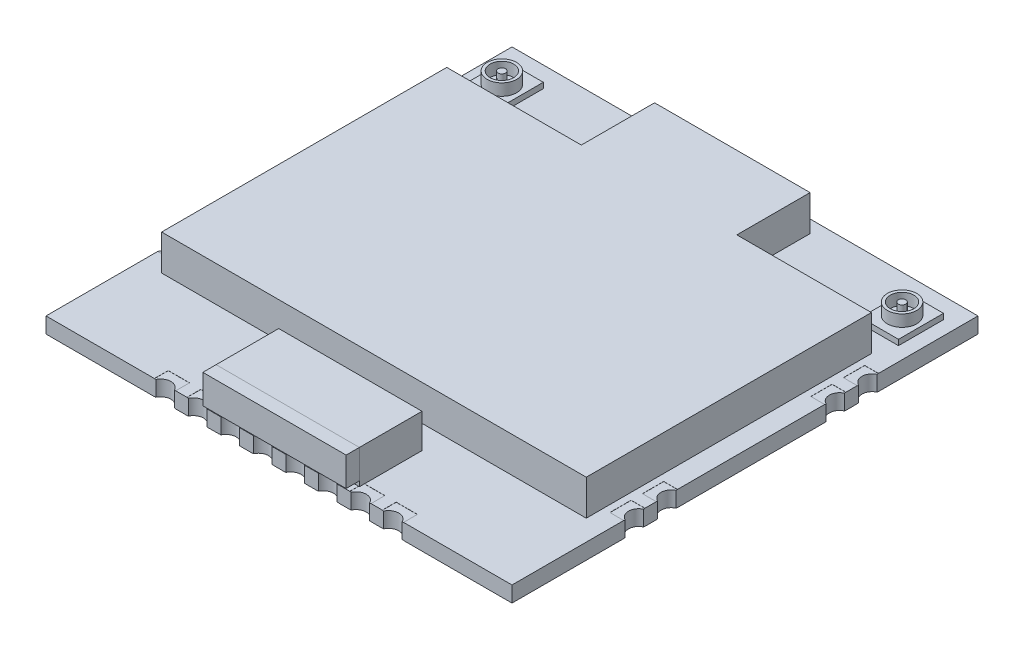
SolidWorks part; units mm, degrees
ref_plane "Front Plane" through (0, 0, 0) normal (0, 0, 1) x (1, 0, 0)
ref_plane "Top Plane" through (0, 0, 0) normal (0, 1, 0) x (1, 0, 0)
ref_plane "Right Plane" through (0, 0, 0) normal (1, 0, 0) x (0, 0, -1)
sketch "Sketch1" plane through (0, 0, 0) normal (0, 1, 0) x (1, 0, 0)
  line L0 (-0.039, 840.9703) -> (812.761, 840.9703) construction
  line L1 (-28.3029, -414.02) -> (-28.3029, -406.4) construction
  line L2 (406.4, 406.4) -> (44.4319, 406.4)
  line L3 (406.4, 406.4) -> (406.4, 230.4034)
  line L4 (406.4, -406.4) -> (214.884, -406.4)
  line L5 (-406.4, 406.4) -> (-406.4, 230.4034)
  line L6 (406.4, 406.4) -> (-406.4, -406.4) construction
  line L7 (406.4, -406.4) -> (-406.4, 406.4) construction
  line L8 (-414.02, -193.04) -> (-406.4, -193.04) construction
  line L9 (-85.1202, -414.02) -> (-85.1202, -406.4) construction
  line L10 (-141.9376, -414.02) -> (-141.9376, -406.4) construction
  line L11 (-198.755, -414.02) -> (-198.755, -406.4) construction
  line L12 (0, 0) -> (0, 406.4) construction
  line L13 (198.755, -414.02) -> (198.755, -406.4) construction
  line L14 (141.9376, -414.02) -> (141.9376, -406.4) construction
  line L15 (85.1202, -414.02) -> (85.1202, -406.4) construction
  line L16 (28.3029, -414.02) -> (28.3029, -406.4) construction
  line L17 (-28.3029, -406.4) -> (-44.4319, -406.4) construction
  line L18 (-44.4319, -406.4) -> (-68.9912, -406.4)
  line L19 (-12.1739, -406.4) -> (-28.3029, -406.4) construction
  line L20 (-68.9912, -406.4) -> (-85.1202, -406.4) construction
  line L21 (-101.2492, -406.4) -> (-125.8086, -406.4)
  line L22 (-85.1202, -406.4) -> (-101.2492, -406.4) construction
  line L23 (-125.8086, -406.4) -> (-141.9376, -406.4) construction
  line L24 (-158.0666, -406.4) -> (-182.626, -406.4)
  line L25 (-141.9376, -406.4) -> (-158.0666, -406.4) construction
  line L26 (-182.626, -406.4) -> (-198.755, -406.4) construction
  line L27 (-214.884, -406.4) -> (-406.4, -406.4)
  line L28 (-198.755, -406.4) -> (-214.884, -406.4) construction
  line L29 (44.4319, -406.4) -> (28.3029, -406.4) construction
  line L30 (12.1739, -406.4) -> (-12.1739, -406.4)
  line L31 (28.3029, -406.4) -> (12.1739, -406.4) construction
  line L32 (101.2492, -406.4) -> (85.1202, -406.4) construction
  line L33 (68.9912, -406.4) -> (44.4319, -406.4)
  line L34 (85.1202, -406.4) -> (68.9912, -406.4) construction
  line L35 (158.0666, -406.4) -> (141.9376, -406.4) construction
  line L36 (125.8086, -406.4) -> (101.2492, -406.4)
  line L37 (141.9376, -406.4) -> (125.8086, -406.4) construction
  line L38 (214.884, -406.4) -> (198.755, -406.4) construction
  line L39 (182.626, -406.4) -> (158.0666, -406.4)
  line L40 (198.755, -406.4) -> (182.626, -406.4) construction
  line L41 (-414.02, -136.2456) -> (-406.4, -136.2456) construction
  line L42 (-414.02, 157.48) -> (-406.4, 157.48) construction
  line L43 (-414.02, 214.2744) -> (-406.4, 214.2744) construction
  line L45 (414.02, 214.2744) -> (406.4, 214.2744) construction
  line L46 (414.02, 157.48) -> (406.4, 157.48) construction
  line L47 (414.02, -136.2456) -> (406.4, -136.2456) construction
  line L48 (414.02, -193.04) -> (406.4, -193.04) construction
  line L49 (-406.4, -193.04) -> (-406.4, -209.169) construction
  line L50 (-406.4, -209.169) -> (-406.4, -406.4)
  line L51 (-406.4, -176.911) -> (-406.4, -193.04) construction
  line L52 (-406.4, -136.2456) -> (-406.4, -152.3746) construction
  line L53 (-406.4, -152.3746) -> (-406.4, -176.911)
  line L54 (-406.4, -120.1166) -> (-406.4, -136.2456) construction
  line L55 (-406.4, 157.48) -> (-406.4, 141.351) construction
  line L56 (-406.4, 141.351) -> (-406.4, -120.1166)
  line L57 (-406.4, 173.609) -> (-406.4, 157.48) construction
  line L58 (-406.4, 214.2744) -> (-406.4, 198.1454) construction
  line L59 (-406.4, 198.1454) -> (-406.4, 173.609)
  line L60 (-406.4, 230.4034) -> (-406.4, 214.2744) construction
  line L61 (406.4, -176.911) -> (406.4, -193.04) construction
  line L62 (406.4, -209.169) -> (406.4, -406.4)
  line L63 (406.4, -193.04) -> (406.4, -209.169) construction
  line L64 (406.4, -120.1166) -> (406.4, -136.2456) construction
  line L65 (406.4, -152.3746) -> (406.4, -176.911)
  line L66 (406.4, -136.2456) -> (406.4, -152.3746) construction
  line L67 (406.4, 173.609) -> (406.4, 157.48) construction
  line L68 (406.4, 141.351) -> (406.4, -120.1166)
  line L69 (406.4, 157.48) -> (406.4, 141.351) construction
  line L70 (406.4, 230.4034) -> (406.4, 214.2744) construction
  line L71 (406.4, 198.1454) -> (406.4, 173.609)
  line L72 (406.4, 214.2744) -> (406.4, 198.1454) construction
  line L73 (-55, 0) -> (55, 0) construction
  line L74 (28.3029, 414.02) -> (28.3029, 406.4) construction
  line L75 (-28.3029, 414.02) -> (-28.3029, 406.4) construction
  line L76 (-28.3029, 406.4) -> (-44.4319, 406.4) construction
  line L77 (-44.4319, 406.4) -> (-406.4, 406.4)
  line L78 (-12.1739, 406.4) -> (-28.3029, 406.4) construction
  line L79 (28.3029, 406.4) -> (12.1739, 406.4) construction
  line L80 (12.1739, 406.4) -> (-12.1739, 406.4)
  line L81 (44.4319, 406.4) -> (28.3029, 406.4) construction
  arc A0 (-12.1739, -406.4) -> (-44.4319, -406.4) centre (-28.3029, -414.02) ccw
  arc A1 (-406.4, -209.169) -> (-406.4, -176.911) centre (-414.02, -193.04) ccw
  arc A2 (-68.9912, -406.4) -> (-101.2492, -406.4) centre (-85.1202, -414.02) ccw
  arc A3 (-125.8086, -406.4) -> (-158.0666, -406.4) centre (-141.9376, -414.02) ccw
  arc A4 (-182.626, -406.4) -> (-214.884, -406.4) centre (-198.755, -414.02) ccw
  arc A5 (182.626, -406.4) -> (214.884, -406.4) centre (198.755, -414.02) cw
  arc A6 (125.8086, -406.4) -> (158.0666, -406.4) centre (141.9376, -414.02) cw
  arc A7 (68.9912, -406.4) -> (101.2492, -406.4) centre (85.1202, -414.02) cw
  arc A8 (12.1739, -406.4) -> (44.4319, -406.4) centre (28.3029, -414.02) cw
  arc A9 (-406.4, -152.3746) -> (-406.4, -120.1166) centre (-414.02, -136.2456) ccw
  arc A10 (-406.4, 141.351) -> (-406.4, 173.609) centre (-414.02, 157.48) ccw
  arc A11 (-406.4, 198.1454) -> (-406.4, 230.4034) centre (-414.02, 214.2744) ccw
  arc A12 (406.4, 198.1454) -> (406.4, 230.4034) centre (414.02, 214.2744) cw
  arc A13 (406.4, 141.351) -> (406.4, 173.609) centre (414.02, 157.48) cw
  arc A14 (406.4, -152.3746) -> (406.4, -120.1166) centre (414.02, -136.2456) cw
  arc A15 (406.4, -209.169) -> (406.4, -176.911) centre (414.02, -193.04) cw
  arc A16 (12.1739, 406.4) -> (44.4319, 406.4) centre (28.3029, 414.02) ccw
  arc A17 (-12.1739, 406.4) -> (-44.4319, 406.4) centre (-28.3029, 414.02) cw
  point P2 (0, 0)
  point P46 (0, 0)
  point P51 (0, 0)
  dimension "D4" = 28.3029
  dimension "D1" = 812.8
  dimension "D2" = 812.8
  dimension "D3" = 812.8
  dimension "D5" = 7.62
  dimension "D6" = 32.258
  dimension "D8" = 397.51
  dimension "D11" = 213.36
  dimension "D12" = 56.7944
  dimension "D13" = 350.52
  dimension "D7" = 4
  dimension "D9" = 2
  dimension "D10" = 2
extrude "Boss-Extrude1" add sketch "Sketch1" along normal blind 27.432
scale "Scale1" scale about origin uniform scaling yes scale factor 0.03937
sketch "Sketch2" plane through (0, 1.08, 0) normal (0, 1, 0) x (1, 0, 0)
  line L0 (0, -16) -> (0, 16) construction
  line L1 (-0.4793, -16) -> (0.4793, -16) construction
  line L3 (14.58, -9.48) -> (-14.58, -9.48)
  line L4 (-14.58, -9.48) -> (-14.58, 10.1)
  line L5 (-14.58, 10.1) -> (-5.34, 10.1)
  line L6 (-5.34, 10.1) -> (-5.34, 15.13)
  line L7 (-5.34, 15.13) -> (5.34, 15.13)
  line L8 (5.34, 10.1) -> (5.34, 15.13)
  line L9 (14.58, 10.1) -> (5.34, 10.1)
  line L10 (14.58, -9.48) -> (14.58, 10.1)
  line L11 (-16, -16) -> (-8.46, -16) construction
  line L12 (0.4793, 16) -> (-0.4793, 16) construction
  point P4 (0, 16)
  point P13 (0, 15.13)
  point P16 (0, -9.48)
  dimension "D1" = 29.16
  dimension "D2" = 19.58
  dimension "D3" = 10.68
  dimension "D4" = 24.61
  dimension "D5" = 6.52
extrude "Boss-Extrude2" add sketch "Sketch2" along normal blind 2.44 separate body
sketch "Sketch3" plane through (0, 1.08, 0) normal (0, 1, 0) x (1, 0, 0)
  line L0 (-16, 16) -> (-16, 9.071) construction
  line L1 (-17.55, 7.706) -> (-15.05, 7.706)
  line L2 (-17.55, 7.706) -> (-17.55, 9.166)
  line L3 (-17.55, 9.166) -> (-15.05, 9.166)
  line L4 (-15.05, 7.706) -> (-15.05, 9.166)
  line L5 (-17.55, 7.706) -> (-15.05, 9.166) construction
  line L6 (-17.55, 9.166) -> (-15.05, 7.706) construction
  line L7 (-6.3193, -17.55) -> (-4.8593, -15.05) construction
  line L8 (-17.55, 5.47) -> (-15.05, 5.47)
  line L9 (-17.55, 5.47) -> (-17.55, 6.93)
  line L10 (-17.55, 6.93) -> (-15.05, 6.93)
  line L11 (-15.05, 5.47) -> (-15.05, 6.93)
  line L12 (-17.55, 5.47) -> (-15.05, 6.93) construction
  line L13 (-17.55, 6.93) -> (-15.05, 5.47) construction
  line L14 (-17.55, -6.094) -> (-15.05, -6.094)
  line L15 (-17.55, -6.094) -> (-17.55, -4.634)
  line L16 (-17.55, -4.634) -> (-15.05, -4.634)
  line L17 (-15.05, -6.094) -> (-15.05, -4.634)
  line L18 (-17.55, -6.094) -> (-15.05, -4.634) construction
  line L19 (-17.55, -4.634) -> (-15.05, -6.094) construction
  line L20 (-17.55, -8.33) -> (-15.05, -8.33)
  line L21 (-17.55, -8.33) -> (-17.55, -6.87)
  line L22 (-17.55, -6.87) -> (-15.05, -6.87)
  line L23 (-15.05, -8.33) -> (-15.05, -6.87)
  line L24 (-17.55, -8.33) -> (-15.05, -6.87) construction
  line L25 (-17.55, -6.87) -> (-15.05, -8.33) construction
  line L26 (-8.555, -17.55) -> (-7.095, -17.55)
  line L27 (-8.555, -17.55) -> (-8.555, -15.05)
  line L28 (-8.555, -15.05) -> (-7.095, -15.05)
  line L29 (-7.095, -17.55) -> (-7.095, -15.05)
  line L30 (-8.555, -17.55) -> (-7.095, -15.05) construction
  line L31 (-8.555, -15.05) -> (-7.095, -17.55) construction
  line L32 (-6.3193, -15.05) -> (-4.8593, -17.55) construction
  line L33 (-6.3193, -17.55) -> (-6.3193, -15.05)
  line L34 (-6.3193, -17.55) -> (-4.8593, -17.55)
  line L35 (-4.8593, -17.55) -> (-4.8593, -15.05)
  line L36 (-6.3193, -15.05) -> (-4.8593, -15.05)
  line L37 (-4.0836, -17.55) -> (-2.6236, -15.05) construction
  line L38 (-4.0836, -15.05) -> (-2.6236, -17.55) construction
  line L39 (-4.0836, -17.55) -> (-4.0836, -15.05)
  line L40 (-4.0836, -17.55) -> (-2.6236, -17.55)
  line L41 (-2.6236, -17.55) -> (-2.6236, -15.05)
  line L42 (-4.0836, -15.05) -> (-2.6236, -15.05)
  line L43 (-1.8479, -17.55) -> (-0.3879, -15.05) construction
  line L44 (-1.8479, -15.05) -> (-0.3879, -17.55) construction
  line L45 (-1.8479, -17.55) -> (-1.8479, -15.05)
  line L46 (-1.8479, -17.55) -> (-0.3879, -17.55)
  line L47 (-0.3879, -17.55) -> (-0.3879, -15.05)
  line L48 (-1.8479, -15.05) -> (-0.3879, -15.05)
  line L49 (0, -16) -> (0, 16) construction
  line L50 (1.8479, -15.05) -> (0.3879, -17.55) construction
  line L51 (1.8479, -17.55) -> (0.3879, -15.05) construction
  line L52 (4.0836, -15.05) -> (2.6236, -17.55) construction
  line L53 (4.0836, -17.55) -> (2.6236, -15.05) construction
  line L54 (-0.4793, -16) -> (0.4793, -16) construction
  line L55 (-1.936, 0) -> (1.936, 0) construction
  line L56 (6.3193, -15.05) -> (4.8593, -17.55) construction
  line L57 (8.555, -15.05) -> (7.095, -17.55) construction
  line L58 (8.555, -17.55) -> (7.095, -15.05) construction
  line L59 (17.55, -6.87) -> (15.05, -8.33) construction
  line L60 (17.55, -8.33) -> (15.05, -6.87) construction
  line L61 (17.55, -4.634) -> (15.05, -6.094) construction
  line L62 (17.55, -6.094) -> (15.05, -4.634) construction
  line L63 (17.55, 6.93) -> (15.05, 5.47) construction
  line L64 (17.55, 5.47) -> (15.05, 6.93) construction
  line L65 (6.3193, -17.55) -> (4.8593, -15.05) construction
  line L66 (17.55, 9.166) -> (15.05, 7.706) construction
  line L67 (17.55, 7.706) -> (15.05, 9.166) construction
  line L68 (1.8479, -15.05) -> (0.3879, -15.05)
  line L69 (0.3879, -17.55) -> (0.3879, -15.05)
  line L70 (1.8479, -17.55) -> (0.3879, -17.55)
  line L71 (1.8479, -17.55) -> (1.8479, -15.05)
  line L72 (4.0836, -15.05) -> (2.6236, -15.05)
  line L73 (2.6236, -17.55) -> (2.6236, -15.05)
  line L74 (4.0836, -17.55) -> (2.6236, -17.55)
  line L75 (4.0836, -17.55) -> (4.0836, -15.05)
  line L76 (6.3193, -15.05) -> (4.8593, -15.05)
  line L77 (4.8593, -17.55) -> (4.8593, -15.05)
  line L78 (6.3193, -17.55) -> (4.8593, -17.55)
  line L79 (6.3193, -17.55) -> (6.3193, -15.05)
  line L80 (7.095, -17.55) -> (7.095, -15.05)
  line L81 (8.555, -15.05) -> (7.095, -15.05)
  line L82 (8.555, -17.55) -> (8.555, -15.05)
  line L83 (8.555, -17.55) -> (7.095, -17.55)
  line L84 (15.05, -8.33) -> (15.05, -6.87)
  line L85 (17.55, -6.87) -> (15.05, -6.87)
  line L86 (17.55, -8.33) -> (17.55, -6.87)
  line L87 (17.55, -8.33) -> (15.05, -8.33)
  line L88 (15.05, -6.094) -> (15.05, -4.634)
  line L89 (17.55, -4.634) -> (15.05, -4.634)
  line L90 (17.55, -6.094) -> (17.55, -4.634)
  line L91 (17.55, -6.094) -> (15.05, -6.094)
  line L92 (15.05, 5.47) -> (15.05, 6.93)
  line L93 (17.55, 6.93) -> (15.05, 6.93)
  line L94 (17.55, 5.47) -> (17.55, 6.93)
  line L95 (17.55, 5.47) -> (15.05, 5.47)
  line L96 (15.05, 7.706) -> (15.05, 9.166)
  line L97 (17.55, 9.166) -> (15.05, 9.166)
  line L98 (17.55, 7.706) -> (17.55, 9.166)
  line L99 (17.55, 7.706) -> (15.05, 7.706)
  line L100 (0.4793, 16) -> (-0.4793, 16) construction
  line L101 (1.8479, 17.55) -> (0.3879, 15.05) construction
  line L102 (1.8479, 15.05) -> (0.3879, 17.55) construction
  line L103 (-1.8479, 15.05) -> (-0.3879, 17.55) construction
  line L104 (-1.8479, 17.55) -> (-0.3879, 15.05) construction
  line L105 (1.8479, 17.55) -> (1.8479, 15.05)
  line L106 (1.8479, 17.55) -> (0.3879, 17.55)
  line L107 (0.3879, 17.55) -> (0.3879, 15.05)
  line L108 (1.8479, 15.05) -> (0.3879, 15.05)
  line L109 (-1.8479, 15.05) -> (-0.3879, 15.05)
  line L110 (-0.3879, 17.55) -> (-0.3879, 15.05)
  line L111 (-1.8479, 17.55) -> (-0.3879, 17.55)
  line L112 (-1.8479, 17.55) -> (-1.8479, 15.05)
  arc A1 (-0.4793, -16) -> (-1.7493, -16) centre (-1.1143, -16.3) ccw construction
  point P0 (-16.3, 8.436)
  point P8 (-16.3, 6.2)
  point P14 (-16.3, -5.364)
  point P20 (-16.3, -7.6)
  point P26 (-7.825, -16.3)
  point P32 (0, 0)
  point P33 (-5.5893, -16.3)
  point P38 (-3.3536, -16.3)
  point P43 (-1.1179, -16.3)
  point P57 (0, 16)
  point P62 (-1.1143, -15.5977)
  point P90 (1.1143, -15.5977)
  point P91 (1.1179, -16.3)
  point P92 (3.3536, -16.3)
  point P93 (5.5893, -16.3)
  point P94 (7.825, -16.3)
  point P95 (16.3, -7.6)
  point P96 (16.3, -5.364)
  point P97 (16.3, 6.2)
  point P98 (16.3, 8.436)
  point P99 (0, 0)
  point P111 (1.1179, 16.3)
  point P112 (1.1143, 15.5977)
  point P113 (-1.1143, 15.5977)
  point P114 (-1.1179, 16.3)
  dimension "D1" = 0.95
  dimension "D2" = 1.46
  dimension "D4" = 6.7071
  dimension "D3" = 4
extrude "Cut-Extrude1" cut sketch "Sketch3" against normal blind 0.01
extrude "Cut-Extrude2" cut sketch "Sketch3<2>" along normal blind 0.01 from surface starting at face at (0, 0, 4.5725)
sketch "Sketch3<2>" plane through (0, 1.08, 0) normal (0, 1, 0) x (1, 0, 0) same geometry as "Sketch3"
sketch "Sketch4" plane through (0, 1.08, 0) normal (0, 1, 0) x (1, 0, 0)
  line L0 (-16, 16) -> (-16, 9.166) construction
  line L1 (-15.04, 11.5) -> (-12.44, 11.5)
  line L2 (-15.04, 11.5) -> (-15.04, 14.59)
  line L3 (-15.04, 14.59) -> (-12.44, 14.59)
  line L4 (-12.44, 11.5) -> (-12.44, 14.59)
  line L5 (-15.04, 11.5) -> (-12.44, 14.59) construction
  line L6 (-15.04, 14.59) -> (-12.44, 11.5) construction
  line L7 (16, 16) -> (1.8479, 16) construction
  point P0 (-13.74, 13.045)
  dimension "D1" = 3.09
  dimension "D2" = 2.6
  dimension "D3" = 0.96
  dimension "D4" = 1.41
extrude "Boss-Extrude3" add sketch "Sketch4" along normal blind 0.38 separate body
sketch "Sketch5" plane through (0, 1.46, 0) normal (0, 1, 0) x (1, 0, 0)
  line L0 (-15.04, 14.59) -> (-12.44, 11.5) construction
  circle A0 centre (-13.74, 13.045) radius 1.01
  circle A1 centre (-13.74, 13.045) radius 0.81
  circle A2 centre (-13.74, 13.045) radius 0.255
  dimension "D1" = 2.02
  dimension "D2" = 0.2
  dimension "D3" = 0.51
extrude "Boss-Extrude4" add sketch "Sketch5" along normal blind 0.8 separate body contours L0 A0 A1 | A0 L0 A1 | L0 A2 | A2 L0 region at (-13.3241, 1.46, -13.9386) region at (-14.3445, 1.46, -13.7256) region at (-13.6572, 1.46, -13.1147) region at (-13.8228, 1.46, -12.9753)
mirror "Mirror2" about plane through (0, 0, 0) normal (1, 0, 0) of bodies 107 106 108
sketch "Sketch7" plane through (0, 0, 0) normal (1, 0, 0) x (0, 0, -1)
  line L0 (-15.4, 1.08) -> (-15.4, 3.42)
  line L1 (-16, 1.08) -> (-8.33, 1.08) construction
  line L2 (-15.4, 3.42) -> (-11.1, 3.42)
  line L3 (-11.1, 3.42) -> (-11.1, 1.08)
  line L4 (-11.1, 1.08) -> (-15.4, 1.08)
  line L5 (-16, 1.08) -> (-16, 0) construction
  dimension "D1" = 0.6
  dimension "D2" = 4.3
  dimension "D3" = 2.34
extrude "Boss-Extrude5" add sketch "Sketch7" along normal mid plane 9.84 separate body
sketch "Sketch8" plane through (0, 0, 0) normal (1, 0, 0) x (0, 0, -1)
  line L0 (-15.4, 3.42) -> (-16.31, 3.42)
  line L1 (-16.31, 3.42) -> (-16.31, 1.43)
  line L2 (-16.31, 1.43) -> (-15.4, 1.43)
  line L3 (-15.4, 3.42) -> (-15.4, 1.08) construction
  line L4 (-15.4, 1.43) -> (-15.4, 3.42)
  line L5 (-11.1, 1.08) -> (-11.1, 3.42) construction
  line L6 (-16, 1.08) -> (-8.33, 1.08) construction
  dimension "D1" = 5.21
  dimension "D2" = 0.35
extrude "Boss-Extrude6" add sketch "Sketch8" along normal mid plane 9.84 separate body
sketch "Sketch9" plane through (0, 0, 0) normal (0, -1, 0) x (1, 0, 0)
  line L1 (-13.55, -14.95) -> (13.55, -14.95) construction
  line L2 (-13.55, -14.95) -> (-13.55, 13.29) construction
  line L3 (-13.55, 13.29) -> (13.55, 13.29) construction
  line L4 (13.55, -14.95) -> (13.55, 13.29) construction
  line L5 (-13.55, -14.95) -> (13.55, 13.29) construction
  line L6 (-13.55, 13.29) -> (13.55, -14.95) construction
  line L7 (-1.8479, -15.05) -> (-0.3879, -15.05) construction
  line L8 (-9.6786, 13.29) -> (-5.8071, 13.29)
  line L9 (-13.55, 13.29) -> (-9.6786, 13.29)
  line L10 (-13.55, 13.29) -> (-13.55, 9.76)
  line L11 (-13.55, 9.76) -> (-9.6786, 9.76)
  line L12 (-9.6786, 13.29) -> (-9.6786, 9.76)
  line L13 (-9.6786, 13.29) -> (-9.6786, 9.76)
  line L14 (-9.6786, 9.76) -> (-5.8071, 9.76)
  line L15 (-5.8071, 13.29) -> (-5.8071, 9.76)
  line L16 (-5.8071, 13.29) -> (-1.9357, 13.29)
  line L17 (-5.8071, 13.29) -> (-5.8071, 9.76)
  line L18 (-5.8071, 9.76) -> (-1.9357, 9.76)
  line L19 (-1.9357, 13.29) -> (-1.9357, 9.76)
  line L20 (-1.9357, 13.29) -> (1.9357, 13.29)
  line L21 (-1.9357, 13.29) -> (-1.9357, 9.76)
  line L22 (-1.9357, 9.76) -> (1.9357, 9.76)
  line L23 (1.9357, 13.29) -> (1.9357, 9.76)
  line L24 (1.9357, 13.29) -> (5.8071, 13.29)
  line L25 (1.9357, 13.29) -> (1.9357, 9.76)
  line L26 (1.9357, 9.76) -> (5.8071, 9.76)
  line L27 (5.8071, 13.29) -> (5.8071, 9.76)
  line L28 (5.8071, 13.29) -> (9.6786, 13.29)
  line L29 (5.8071, 13.29) -> (5.8071, 9.76)
  line L30 (5.8071, 9.76) -> (9.6786, 9.76)
  line L31 (9.6786, 13.29) -> (9.6786, 9.76)
  line L32 (9.6786, 13.29) -> (13.55, 13.29)
  line L33 (9.6786, 13.29) -> (9.6786, 9.76)
  line L34 (9.6786, 9.76) -> (13.55, 9.76)
  line L35 (13.55, 13.29) -> (13.55, 9.76)
  line L36 (-9.6786, 9.76) -> (-5.8071, 9.76)
  line L37 (-9.6786, 9.76) -> (-9.6786, 6.23)
  line L38 (-9.6786, 6.23) -> (-5.8071, 6.23)
  line L39 (-5.8071, 9.76) -> (-5.8071, 6.23)
  line L40 (-5.8071, 9.76) -> (-1.9357, 9.76)
  line L41 (-5.8071, 9.76) -> (-5.8071, 6.23)
  line L42 (-5.8071, 6.23) -> (-1.9357, 6.23)
  line L43 (-1.9357, 9.76) -> (-1.9357, 6.23)
  line L44 (-1.9357, 9.76) -> (1.9357, 9.76)
  line L45 (-1.9357, 9.76) -> (-1.9357, 6.23)
  line L46 (-1.9357, 6.23) -> (1.9357, 6.23)
  line L47 (1.9357, 9.76) -> (1.9357, 6.23)
  line L48 (1.9357, 9.76) -> (5.8071, 9.76)
  line L49 (1.9357, 9.76) -> (1.9357, 6.23)
  line L50 (1.9357, 6.23) -> (5.8071, 6.23)
  line L51 (5.8071, 9.76) -> (5.8071, 6.23)
  line L52 (5.8071, 9.76) -> (9.6786, 9.76)
  line L53 (5.8071, 9.76) -> (5.8071, 6.23)
  line L54 (5.8071, 6.23) -> (9.6786, 6.23)
  line L55 (9.6786, 9.76) -> (9.6786, 6.23)
  line L56 (9.6786, 9.76) -> (13.55, 9.76)
  line L57 (9.6786, 9.76) -> (9.6786, 6.23)
  line L58 (9.6786, 6.23) -> (13.55, 6.23)
  line L59 (13.55, 9.76) -> (13.55, 6.23)
  line L60 (-9.6786, 6.23) -> (-5.8071, 6.23)
  line L61 (-9.6786, 6.23) -> (-9.6786, 2.7)
  line L62 (-9.6786, 2.7) -> (-5.8071, 2.7)
  line L63 (-5.8071, 6.23) -> (-5.8071, 2.7)
  line L64 (-5.8071, 6.23) -> (-1.9357, 6.23)
  line L65 (-5.8071, 6.23) -> (-5.8071, 2.7)
  line L66 (-5.8071, 2.7) -> (-1.9357, 2.7)
  line L67 (-1.9357, 6.23) -> (-1.9357, 2.7)
  line L68 (-1.9357, 6.23) -> (1.9357, 6.23)
  line L69 (-1.9357, 6.23) -> (-1.9357, 2.7)
  line L70 (-1.9357, 2.7) -> (1.9357, 2.7)
  line L71 (1.9357, 6.23) -> (1.9357, 2.7)
  line L72 (1.9357, 6.23) -> (5.8071, 6.23)
  line L73 (1.9357, 6.23) -> (1.9357, 2.7)
  line L74 (1.9357, 2.7) -> (5.8071, 2.7)
  line L75 (5.8071, 6.23) -> (5.8071, 2.7)
  line L76 (5.8071, 6.23) -> (9.6786, 6.23)
  line L77 (5.8071, 6.23) -> (5.8071, 2.7)
  line L78 (5.8071, 2.7) -> (9.6786, 2.7)
  line L79 (9.6786, 6.23) -> (9.6786, 2.7)
  line L80 (9.6786, 6.23) -> (13.55, 6.23)
  line L81 (9.6786, 6.23) -> (9.6786, 2.7)
  line L82 (9.6786, 2.7) -> (13.55, 2.7)
  line L83 (13.55, 6.23) -> (13.55, 2.7)
  line L84 (-9.6786, 2.7) -> (-5.8071, 2.7)
  line L85 (-9.6786, 2.7) -> (-9.6786, -0.83)
  line L86 (-9.6786, -0.83) -> (-5.8071, -0.83)
  line L87 (-5.8071, 2.7) -> (-5.8071, -0.83)
  line L88 (-5.8071, 2.7) -> (-1.9357, 2.7)
  line L89 (-5.8071, 2.7) -> (-5.8071, -0.83)
  line L90 (-5.8071, -0.83) -> (-1.9357, -0.83)
  line L91 (-1.9357, 2.7) -> (-1.9357, -0.83)
  line L92 (-1.9357, 2.7) -> (1.9357, 2.7)
  line L93 (-1.9357, 2.7) -> (-1.9357, -0.83)
  line L94 (-1.9357, -0.83) -> (1.9357, -0.83)
  line L95 (1.9357, 2.7) -> (1.9357, -0.83)
  line L96 (1.9357, 2.7) -> (5.8071, 2.7)
  line L97 (1.9357, 2.7) -> (1.9357, -0.83)
  line L98 (1.9357, -0.83) -> (5.8071, -0.83)
  line L99 (5.8071, 2.7) -> (5.8071, -0.83)
  line L100 (5.8071, 2.7) -> (9.6786, 2.7)
  line L101 (5.8071, 2.7) -> (5.8071, -0.83)
  line L102 (5.8071, -0.83) -> (9.6786, -0.83)
  line L103 (9.6786, 2.7) -> (9.6786, -0.83)
  line L104 (9.6786, 2.7) -> (13.55, 2.7)
  line L105 (9.6786, 2.7) -> (9.6786, -0.83)
  line L106 (9.6786, -0.83) -> (13.55, -0.83)
  line L107 (13.55, 2.7) -> (13.55, -0.83)
  line L108 (-9.6786, -0.83) -> (-5.8071, -0.83)
  line L109 (-9.6786, -0.83) -> (-9.6786, -4.36)
  line L110 (-9.6786, -4.36) -> (-5.8071, -4.36)
  line L111 (-5.8071, -0.83) -> (-5.8071, -4.36)
  line L112 (-5.8071, -0.83) -> (-1.9357, -0.83)
  line L113 (-5.8071, -0.83) -> (-5.8071, -4.36)
  line L114 (-5.8071, -4.36) -> (-1.9357, -4.36)
  line L115 (-1.9357, -0.83) -> (-1.9357, -4.36)
  line L116 (-1.9357, -0.83) -> (1.9357, -0.83)
  line L117 (-1.9357, -0.83) -> (-1.9357, -4.36)
  line L118 (-1.9357, -4.36) -> (1.9357, -4.36)
  line L119 (1.9357, -0.83) -> (1.9357, -4.36)
  line L120 (1.9357, -0.83) -> (5.8071, -0.83)
  line L121 (1.9357, -0.83) -> (1.9357, -4.36)
  line L122 (1.9357, -4.36) -> (5.8071, -4.36)
  line L123 (5.8071, -0.83) -> (5.8071, -4.36)
  line L124 (5.8071, -0.83) -> (9.6786, -0.83)
  line L125 (5.8071, -0.83) -> (5.8071, -4.36)
  line L126 (5.8071, -4.36) -> (9.6786, -4.36)
  line L127 (9.6786, -0.83) -> (9.6786, -4.36)
  line L128 (9.6786, -0.83) -> (13.55, -0.83)
  line L129 (9.6786, -0.83) -> (9.6786, -4.36)
  line L130 (9.6786, -4.36) -> (13.55, -4.36)
  line L131 (13.55, -0.83) -> (13.55, -4.36)
  line L132 (-9.6786, -4.36) -> (-5.8071, -4.36)
  line L133 (-9.6786, -4.36) -> (-9.6786, -7.89)
  line L134 (-9.6786, -7.89) -> (-5.8071, -7.89)
  line L135 (-5.8071, -4.36) -> (-5.8071, -7.89)
  line L136 (-5.8071, -4.36) -> (-1.9357, -4.36)
  line L137 (-5.8071, -4.36) -> (-5.8071, -7.89)
  line L138 (-5.8071, -7.89) -> (-1.9357, -7.89)
  line L139 (-1.9357, -4.36) -> (-1.9357, -7.89)
  line L140 (-1.9357, -4.36) -> (1.9357, -4.36)
  line L141 (-1.9357, -4.36) -> (-1.9357, -7.89)
  line L142 (-1.9357, -7.89) -> (1.9357, -7.89)
  line L143 (1.9357, -4.36) -> (1.9357, -7.89)
  line L144 (1.9357, -4.36) -> (5.8071, -4.36)
  line L145 (1.9357, -4.36) -> (1.9357, -7.89)
  line L146 (1.9357, -7.89) -> (5.8071, -7.89)
  line L147 (5.8071, -4.36) -> (5.8071, -7.89)
  line L148 (5.8071, -4.36) -> (9.6786, -4.36)
  line L149 (5.8071, -4.36) -> (5.8071, -7.89)
  line L150 (5.8071, -7.89) -> (9.6786, -7.89)
  line L151 (9.6786, -4.36) -> (9.6786, -7.89)
  line L152 (9.6786, -4.36) -> (13.55, -4.36)
  line L153 (9.6786, -4.36) -> (9.6786, -7.89)
  line L154 (9.6786, -7.89) -> (13.55, -7.89)
  line L155 (13.55, -4.36) -> (13.55, -7.89)
  line L156 (-9.6786, -7.89) -> (-5.8071, -7.89)
  line L157 (-9.6786, -7.89) -> (-9.6786, -11.42)
  line L158 (-9.6786, -11.42) -> (-5.8071, -11.42)
  line L159 (-5.8071, -7.89) -> (-5.8071, -11.42)
  line L160 (-5.8071, -7.89) -> (-1.9357, -7.89)
  line L161 (-5.8071, -7.89) -> (-5.8071, -11.42)
  line L162 (-5.8071, -11.42) -> (-1.9357, -11.42)
  line L163 (-1.9357, -7.89) -> (-1.9357, -11.42)
  line L164 (-1.9357, -7.89) -> (1.9357, -7.89)
  line L165 (-1.9357, -7.89) -> (-1.9357, -11.42)
  line L166 (-1.9357, -11.42) -> (1.9357, -11.42)
  line L167 (1.9357, -7.89) -> (1.9357, -11.42)
  line L168 (1.9357, -7.89) -> (5.8071, -7.89)
  line L169 (1.9357, -7.89) -> (1.9357, -11.42)
  line L170 (1.9357, -11.42) -> (5.8071, -11.42)
  line L171 (5.8071, -7.89) -> (5.8071, -11.42)
  line L172 (5.8071, -7.89) -> (9.6786, -7.89)
  line L173 (5.8071, -7.89) -> (5.8071, -11.42)
  line L174 (5.8071, -11.42) -> (9.6786, -11.42)
  line L175 (9.6786, -7.89) -> (9.6786, -11.42)
  line L176 (9.6786, -7.89) -> (13.55, -7.89)
  line L177 (9.6786, -7.89) -> (9.6786, -11.42)
  line L178 (9.6786, -11.42) -> (13.55, -11.42)
  line L179 (13.55, -7.89) -> (13.55, -11.42)
  line L180 (-9.6786, -11.42) -> (-5.8071, -11.42)
  line L181 (-9.6786, -11.42) -> (-9.6786, -14.95)
  line L182 (-9.6786, -14.95) -> (-5.8071, -14.95)
  line L183 (-5.8071, -11.42) -> (-5.8071, -14.95)
  line L184 (-5.8071, -11.42) -> (-1.9357, -11.42)
  line L185 (-5.8071, -11.42) -> (-5.8071, -14.95)
  line L186 (-5.8071, -14.95) -> (-1.9357, -14.95)
  line L187 (-1.9357, -11.42) -> (-1.9357, -14.95)
  line L188 (-1.9357, -11.42) -> (1.9357, -11.42)
  line L189 (-1.9357, -11.42) -> (-1.9357, -14.95)
  line L190 (-1.9357, -14.95) -> (1.9357, -14.95)
  line L191 (1.9357, -11.42) -> (1.9357, -14.95)
  line L192 (1.9357, -11.42) -> (5.8071, -11.42)
  line L193 (1.9357, -11.42) -> (1.9357, -14.95)
  line L194 (1.9357, -14.95) -> (5.8071, -14.95)
  line L195 (5.8071, -11.42) -> (5.8071, -14.95)
  line L196 (5.8071, -11.42) -> (9.6786, -11.42)
  line L197 (5.8071, -11.42) -> (5.8071, -14.95)
  line L198 (5.8071, -14.95) -> (9.6786, -14.95)
  line L199 (9.6786, -11.42) -> (9.6786, -14.95)
  line L200 (9.6786, -11.42) -> (13.55, -11.42)
  line L201 (9.6786, -11.42) -> (9.6786, -14.95)
  line L202 (9.6786, -14.95) -> (13.55, -14.95)
  line L203 (13.55, -11.42) -> (13.55, -14.95)
  line L204 (-13.55, 9.76) -> (-9.6786, 9.76)
  line L205 (-13.55, 9.76) -> (-13.55, 6.23)
  line L206 (-13.55, 6.23) -> (-9.6786, 6.23)
  line L207 (-9.6786, 9.76) -> (-9.6786, 6.23)
  line L208 (-13.55, 6.23) -> (-9.6786, 6.23)
  line L209 (-13.55, 6.23) -> (-13.55, 2.7)
  line L210 (-13.55, 2.7) -> (-9.6786, 2.7)
  line L211 (-9.6786, 6.23) -> (-9.6786, 2.7)
  line L212 (-13.55, 2.7) -> (-9.6786, 2.7)
  line L213 (-13.55, 2.7) -> (-13.55, -0.83)
  line L214 (-13.55, -0.83) -> (-9.6786, -0.83)
  line L215 (-9.6786, 2.7) -> (-9.6786, -0.83)
  line L216 (-13.55, -0.83) -> (-9.6786, -0.83)
  line L217 (-13.55, -0.83) -> (-13.55, -4.36)
  line L218 (-13.55, -4.36) -> (-9.6786, -4.36)
  line L219 (-9.6786, -0.83) -> (-9.6786, -4.36)
  line L220 (-13.55, -4.36) -> (-9.6786, -4.36)
  line L221 (-13.55, -4.36) -> (-13.55, -7.89)
  line L222 (-13.55, -7.89) -> (-9.6786, -7.89)
  line L223 (-9.6786, -4.36) -> (-9.6786, -7.89)
  line L224 (-13.55, -7.89) -> (-9.6786, -7.89)
  line L225 (-13.55, -7.89) -> (-13.55, -11.42)
  line L226 (-13.55, -11.42) -> (-9.6786, -11.42)
  line L227 (-9.6786, -7.89) -> (-9.6786, -11.42)
  line L228 (-13.55, -11.42) -> (-9.6786, -11.42)
  line L229 (-13.55, -11.42) -> (-13.55, -14.95)
  line L230 (-13.55, -14.95) -> (-9.6786, -14.95)
  line L231 (-9.6786, -11.42) -> (-9.6786, -14.95)
  point P0 (0, -0.83)
  point P5 (0, 0)
  point P11 (13.4742, -14.95)
  point P12 (-9.7189, 10.1772)
  dimension "D1" = 27.1
  dimension "D2" = 28.24
  dimension "D3" = 0.1
  dimension "D4" = 7
  dimension "D5" = 8
extrude "Boss-Extrude8" add sketch "Sketch9" along normal blind 0.01 separate body contours L12 L9 L10 L11 | L15 L8 L12 L14 | L39 L14 L37 L38 | L209 L210 L61 L206 | L221 L222 L133 L218 | L229 L230 L181 L226 | L187 L162 L183 L186 | L139 L114 L135 L138 | L159 L134 L157 L158 | L147 L122 L143 L146 | L155 L130 L151 L154 | L203 L178 L199 L202 | L195 L170 L191 L194 | L175 L150 L171 L174 | L167 L142 L163 L166 | L71 L46 L67 L70 | L91 L66 L87 L90 | L43 L18 L39 L42 | L31 L28 L27 L30 | L59 L34 L55 L58 | L79 L54 L75 L78 | L107 L82 L103 L106 | L131 L106 L127 L130 | L23 L20 L19 L22 | L111 L86 L109 L110 | L99 L74 L95 L98 | L213 L214 L85 L210 region at (-11.6143, 0, 11.525) region at (-7.7429, 0, 11.525) region at (-7.7429, 0, 7.995) region at (-3.8714, 0, 7.995) region at (0, 0, 11.525) region at (-11.6143, 0, 4.465) region at (-11.6143, 0, 0.935) region at (0, 0, 4.465) region at (-3.8714, 0, 0.935) region at (7.7429, 0, 11.525) region at (-7.7429, 0, -2.595) region at (-11.6143, 0, -6.125) region at (11.6143, 0, 7.995) region at (7.7429, 0, 4.465) region at (3.8714, 0, 0.935) region at (-3.8714, 0, -6.125) region at (-7.7429, 0, -9.655) region at (-11.6143, 0, -13.185) region at (11.6143, 0, 0.935) region at (3.8714, 0, -6.125) region at (0, 0, -9.655) region at (-3.8714, 0, -13.185) region at (11.6143, 0, -2.595) region at (11.6143, 0, -6.125) region at (7.7429, 0, -9.655) region at (3.8714, 0, -13.185) region at (11.6143, 0, -13.185)
